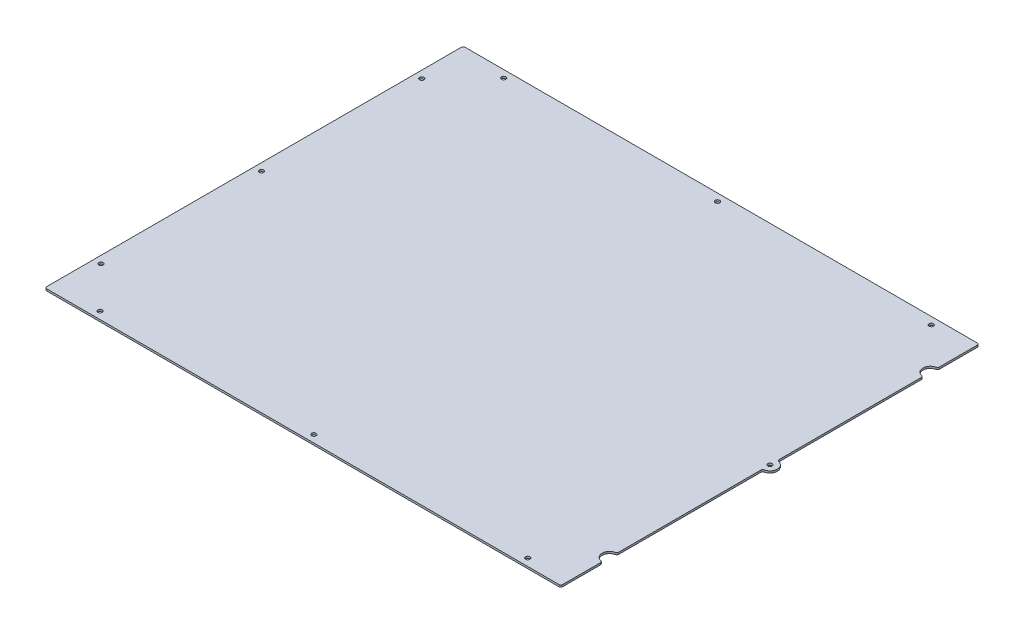
SolidWorks part; units mm, degrees
ref_plane "Front Plane" through (0, 0, 0) normal (0, 0, 1) x (1, 0, 0)
ref_plane "Top Plane" through (0, 0, 0) normal (0, 1, 0) x (1, 0, 0)
ref_plane "Right Plane" through (0, 0, 0) normal (1, 0, 0) x (0, 0, -1)
sketch "Sketch1" plane through (0, 0, 0) normal (0, 1, 0) x (1, 0, 0)
  line L0 (332.232, 273.304) -> (332.232, 219.202) construction
  line L1 (-341.884, -273.304) -> (332.232, -273.304)
  line L2 (-341.884, -273.304) -> (-341.884, 273.304)
  line L3 (-341.884, 273.304) -> (332.232, 273.304)
  line L4 (332.232, -219.202) -> (332.232, -273.304) construction
  line L5 (-341.884, -273.304) -> (341.884, 273.304) construction
  line L6 (-341.884, 273.304) -> (341.884, -273.304) construction
  line L7 (332.232, 273.304) -> (332.232, 219.202)
  line L8 (332.232, 199.898) -> (332.232, 9.652) construction
  line L9 (332.232, 199.898) -> (332.232, 9.652)
  line L10 (332.232, -9.652) -> (332.232, -199.898) construction
  line L11 (332.232, -9.652) -> (332.232, -199.898)
  line L12 (332.232, -219.202) -> (332.232, -273.304)
  arc A0 (332.232, -199.898) -> (332.232, -219.202) centre (332.232, -209.55) ccw
  arc A1 (332.232, -9.652) -> (332.232, 9.652) centre (332.232, 0) ccw
  arc A2 (332.232, 219.202) -> (332.232, 199.898) centre (332.232, 209.55) ccw
  point P0 (0, 0)
  dimension "D4" = 273.304
  dimension "D6" = 19.304
  dimension "D7" = 63.754
  dimension "D3" = 63.754
  dimension "D1" = 674.116
  dimension "D2" = 546.608
extrude "Boss-Extrude1" add sketch "Sketch1" along normal blind 2.54
hole_wizard "#1 (0.228) Diameter Hole2" positions "Sketch4" profile "Sketch5" hole size "#1" standard "ANSI Inch" end condition through all
sketch "Sketch4" plane through (0, 2.54, 0) normal (0, 1, 0) x (1, 0, 0)
  point P0 (332.232, 0)
sketch "Sketch5" plane through (332.232, 2.54, 0) normal (1, 0, 0) x (0, 0, 1)
  line L0 (0, 0) -> (0, 2.54)
  line L1 (0, 2.54) -> (2.8956, 2.54)
  line L2 (2.8956, 2.54) -> (2.8956, 0)
  line L5 (2.8956, 0) -> (0, 0)
  line L11 (0, -6.35) -> (0, 107.95) construction
  dimension "Thru Hole Dia." = 5.7912
  dimension "Thru Hole Depth" = 2.54
fillet "Fillet2" radius 2.54 10 edges at (-341.884, 1.27, -273.304) (-341.884, 1.27, 273.304) (332.232, 1.27, 273.304) (332.232, 1.27, 219.202) (332.232, 1.27, 199.898) (332.232, 1.27, 9.652) (332.232, 1.27, -9.652) (332.232, 1.27, -199.898) (332.232, 1.27, -219.202) (332.232, 1.27, -273.304)
hole_wizard "#1 (0.228) Diameter Hole3" positions "Sketch6" profile "Sketch7" hole size "#1" standard "ANSI Inch" end condition through all
sketch "Sketch6" plane through (0, 2.54, 0) normal (0, 1, 0) x (1, 0, 0)
  point P0 (-279.4, 263.652)
  point P3 (-332.232, 209.55)
  point P6 (0, 263.652)
  point P9 (279.4, 263.652)
  point P12 (279.4, -263.652)
  point P15 (0, -263.652)
  point P18 (-279.4, -263.652)
  point P21 (-332.232, -209.55)
  point P24 (-332.232, 0)
sketch "Sketch7" plane through (-279.4, 2.54, -263.652) normal (1, 0, 0) x (0, 0, 1)
  line L0 (0, 0) -> (0, 2.54)
  line L1 (0, 2.54) -> (2.8956, 2.54)
  line L2 (2.8956, 2.54) -> (2.8956, 0)
  line L5 (2.8956, 0) -> (0, 0)
  line L11 (0, -6.35) -> (0, 107.95) construction
  dimension "Thru Hole Dia." = 5.7912
  dimension "Thru Hole Depth" = 2.54
sketch "Sketch8" plane through (0, 2.54, 0) normal (0, 1, 0) x (1, 0, 0)
  line L1 (-322.58, 254) -> (322.58, 254) construction
  line L2 (-322.58, 254) -> (-322.58, -254) construction
  line L3 (-322.58, -254) -> (322.58, -254) construction
  line L4 (322.58, 254) -> (322.58, -254) construction
  line L6 (-341.884, 270.764) -> (-341.884, -270.764) construction
  line L7 (329.692, 273.304) -> (-339.344, 273.304) construction
  line L9 (-282.2575, 254) -> (-282.2575, -254) construction
  line L10 (-255.3758, 254) -> (-255.3758, -254) construction
  line L11 (-228.4942, 254) -> (-228.4942, -254) construction
  line L12 (-201.6125, 254) -> (-201.6125, -254) construction
  line L13 (-174.7308, 254) -> (-174.7308, -254) construction
  line L14 (-147.8492, 254) -> (-147.8492, -254) construction
  line L15 (-120.9675, 254) -> (-120.9675, -254) construction
  line L16 (-94.0858, 254) -> (-94.0858, -254) construction
  line L17 (-67.2042, 254) -> (-67.2042, -254) construction
  line L18 (-40.3225, 254) -> (-40.3225, -254) construction
  line L19 (-13.4408, 254) -> (-13.4408, -254) construction
  line L20 (13.4408, 254) -> (13.4408, -254) construction
  line L21 (40.3225, 254) -> (40.3225, -254) construction
  line L22 (67.2042, 254) -> (67.2042, -254) construction
  line L23 (94.0858, 254) -> (94.0858, -254) construction
  line L24 (120.9675, 254) -> (120.9675, -254) construction
  line L25 (147.8492, 254) -> (147.8492, -254) construction
  line L26 (174.7308, 254) -> (174.7308, -254) construction
  line L27 (201.6125, 254) -> (201.6125, -254) construction
  line L28 (228.4942, 254) -> (228.4942, -254) construction
  line L29 (255.3758, 254) -> (255.3758, -254) construction
  line L30 (282.2575, 254) -> (282.2575, -254) construction
  line L31 (309.1392, 254) -> (309.1392, -254) construction
  line L32 (-322.58, 190.5) -> (322.58, 190.5) construction
  line L34 (-318.2832, 145.034) -> (-299.9952, 145.034)
  line L35 (-318.2832, 145.034) -> (-318.2832, 235.966)
  line L36 (-318.2832, 235.966) -> (-299.9952, 235.966)
  line L37 (-299.9952, 145.034) -> (-299.9952, 235.966)
  line L38 (-318.2832, 145.034) -> (-299.9952, 235.966) construction
  line L39 (-318.2832, 235.966) -> (-299.9952, 145.034) construction
  line L40 (-273.1135, 145.034) -> (-273.1135, 235.966)
  line L41 (-291.4015, 145.034) -> (-291.4015, 235.966)
  line L42 (-291.4015, 145.034) -> (-273.1135, 145.034)
  line L43 (-264.5198, 235.966) -> (-246.2318, 235.966)
  line L44 (-246.2318, 145.034) -> (-246.2318, 235.966)
  line L45 (-264.5198, 145.034) -> (-264.5198, 235.966)
  line L46 (-264.5198, 145.034) -> (-246.2318, 145.034)
  line L51 (-210.7565, 235.966) -> (-192.4685, 235.966)
  line L52 (-192.4685, 145.034) -> (-192.4685, 235.966)
  line L53 (-210.7565, 145.034) -> (-210.7565, 235.966)
  line L54 (-210.7565, 145.034) -> (-192.4685, 145.034)
  line L55 (-183.8748, 235.966) -> (-165.5868, 235.966)
  line L56 (-165.5868, 145.034) -> (-165.5868, 235.966)
  line L57 (-183.8748, 145.034) -> (-183.8748, 235.966)
  line L58 (-183.8748, 145.034) -> (-165.5868, 145.034)
  line L59 (-156.9932, 235.966) -> (-138.7052, 235.966)
  line L60 (-138.7052, 145.034) -> (-138.7052, 235.966)
  line L61 (-156.9932, 145.034) -> (-156.9932, 235.966)
  line L62 (-156.9932, 145.034) -> (-138.7052, 145.034)
  line L63 (-130.1115, 235.966) -> (-111.8235, 235.966)
  line L64 (-111.8235, 145.034) -> (-111.8235, 235.966)
  line L65 (-130.1115, 145.034) -> (-130.1115, 235.966)
  line L66 (-130.1115, 145.034) -> (-111.8235, 145.034)
  line L71 (-76.3482, 235.966) -> (-58.0602, 235.966)
  line L72 (-58.0602, 145.034) -> (-58.0602, 235.966)
  line L73 (-76.3482, 145.034) -> (-76.3482, 235.966)
  line L74 (-76.3482, 145.034) -> (-58.0602, 145.034)
  line L75 (-49.4665, 235.966) -> (-31.1785, 235.966)
  line L76 (-31.1785, 145.034) -> (-31.1785, 235.966)
  line L77 (-49.4665, 145.034) -> (-49.4665, 235.966)
  line L78 (-49.4665, 145.034) -> (-31.1785, 145.034)
  line L79 (-22.5848, 235.966) -> (-4.2968, 235.966)
  line L80 (-4.2968, 145.034) -> (-4.2968, 235.966)
  line L81 (-22.5848, 145.034) -> (-22.5848, 235.966)
  line L82 (-22.5848, 145.034) -> (-4.2968, 145.034)
  line L83 (4.2968, 235.966) -> (22.5848, 235.966)
  line L84 (22.5848, 145.034) -> (22.5848, 235.966)
  line L85 (4.2968, 145.034) -> (4.2968, 235.966)
  line L86 (4.2968, 145.034) -> (22.5848, 145.034)
  line L87 (31.1785, 235.966) -> (49.4665, 235.966)
  line L88 (49.4665, 145.034) -> (49.4665, 235.966)
  line L89 (31.1785, 145.034) -> (31.1785, 235.966)
  line L90 (31.1785, 145.034) -> (49.4665, 145.034)
  line L91 (58.0602, 235.966) -> (76.3482, 235.966)
  line L92 (76.3482, 145.034) -> (76.3482, 235.966)
  line L93 (58.0602, 145.034) -> (58.0602, 235.966)
  line L94 (58.0602, 145.034) -> (76.3482, 145.034)
  line L95 (87.286, 237.109) -> (100.8857, 237.109)
  line L96 (87.286, 143.891) -> (100.8857, 143.891)
  line L97 (221.6943, 143.891) -> (235.294, 143.891)
  line L98 (221.6943, 237.109) -> (235.294, 237.109)
  line L99 (111.8235, 235.966) -> (130.1115, 235.966)
  line L100 (130.1115, 145.034) -> (130.1115, 235.966)
  line L101 (111.8235, 145.034) -> (111.8235, 235.966)
  line L102 (111.8235, 145.034) -> (130.1115, 145.034)
  line L103 (138.7052, 235.966) -> (156.9932, 235.966)
  line L104 (156.9932, 145.034) -> (156.9932, 235.966)
  line L105 (138.7052, 145.034) -> (138.7052, 235.966)
  line L106 (138.7052, 145.034) -> (156.9932, 145.034)
  line L107 (165.5868, 235.966) -> (183.8748, 235.966)
  line L108 (183.8748, 145.034) -> (183.8748, 235.966)
  line L109 (165.5868, 145.034) -> (165.5868, 235.966)
  line L110 (165.5868, 145.034) -> (183.8748, 145.034)
  line L111 (192.4685, 235.966) -> (210.7565, 235.966)
  line L112 (210.7565, 145.034) -> (210.7565, 235.966)
  line L113 (192.4685, 145.034) -> (192.4685, 235.966)
  line L114 (192.4685, 145.034) -> (210.7565, 145.034)
  line L119 (246.2318, 235.966) -> (264.5198, 235.966)
  line L120 (264.5198, 145.034) -> (264.5198, 235.966)
  line L121 (246.2318, 145.034) -> (246.2318, 235.966)
  line L122 (246.2318, 145.034) -> (264.5198, 145.034)
  line L123 (273.1135, 235.966) -> (291.4015, 235.966)
  line L124 (291.4015, 145.034) -> (291.4015, 235.966)
  line L125 (273.1135, 145.034) -> (273.1135, 235.966)
  line L126 (273.1135, 145.034) -> (291.4015, 145.034)
  line L127 (299.9952, 235.966) -> (318.2832, 235.966)
  line L128 (318.2832, 145.034) -> (318.2832, 235.966)
  line L129 (299.9952, 145.034) -> (299.9952, 235.966)
  line L130 (299.9952, 145.034) -> (318.2832, 145.034)
  line L131 (-291.4015, 108.966) -> (-273.1135, 108.966)
  line L132 (-273.1135, 18.034) -> (-273.1135, 108.966)
  line L133 (-291.4015, 18.034) -> (-291.4015, 108.966)
  line L134 (-291.4015, 18.034) -> (-273.1135, 18.034)
  line L135 (-264.5198, 108.966) -> (-246.2318, 108.966)
  line L136 (-246.2318, 18.034) -> (-246.2318, 108.966)
  line L137 (-264.5198, 18.034) -> (-264.5198, 108.966)
  line L138 (-264.5198, 18.034) -> (-246.2318, 18.034)
  line L139 (-100.8857, 237.109) -> (-87.286, 237.109)
  line L140 (-100.8857, 143.891) -> (-87.286, 143.891)
  line L143 (-210.7565, 108.966) -> (-192.4685, 108.966)
  line L144 (-192.4685, 18.034) -> (-192.4685, 108.966)
  line L145 (-210.7565, 18.034) -> (-210.7565, 108.966)
  line L146 (-210.7565, 18.034) -> (-192.4685, 18.034)
  line L147 (-183.8748, 108.966) -> (-165.5868, 108.966)
  line L148 (-165.5868, 18.034) -> (-165.5868, 108.966)
  line L149 (-183.8748, 18.034) -> (-183.8748, 108.966)
  line L150 (-183.8748, 18.034) -> (-165.5868, 18.034)
  line L151 (-156.9932, 108.966) -> (-138.7052, 108.966)
  line L152 (-138.7052, 18.034) -> (-138.7052, 108.966)
  line L153 (-156.9932, 18.034) -> (-156.9932, 108.966)
  line L154 (-156.9932, 18.034) -> (-138.7052, 18.034)
  line L155 (-130.1115, 108.966) -> (-111.8235, 108.966)
  line L156 (-111.8235, 18.034) -> (-111.8235, 108.966)
  line L157 (-130.1115, 18.034) -> (-130.1115, 108.966)
  line L158 (-130.1115, 18.034) -> (-111.8235, 18.034)
  line L163 (-76.3482, 108.966) -> (-58.0602, 108.966)
  line L164 (-58.0602, 18.034) -> (-58.0602, 108.966)
  line L165 (-76.3482, 18.034) -> (-76.3482, 108.966)
  line L166 (-76.3482, 18.034) -> (-58.0602, 18.034)
  line L167 (-49.4665, 108.966) -> (-31.1785, 108.966)
  line L168 (-31.1785, 18.034) -> (-31.1785, 108.966)
  line L169 (-49.4665, 18.034) -> (-49.4665, 108.966)
  line L170 (-49.4665, 18.034) -> (-31.1785, 18.034)
  line L171 (-22.5848, 108.966) -> (-4.2968, 108.966)
  line L172 (-4.2968, 18.034) -> (-4.2968, 108.966)
  line L173 (-22.5848, 18.034) -> (-22.5848, 108.966)
  line L174 (-22.5848, 18.034) -> (-4.2968, 18.034)
  line L175 (4.2968, 108.966) -> (22.5848, 108.966)
  line L176 (22.5848, 18.034) -> (22.5848, 108.966)
  line L177 (4.2968, 18.034) -> (4.2968, 108.966)
  line L178 (4.2968, 18.034) -> (22.5848, 18.034)
  line L179 (31.1785, 108.966) -> (49.4665, 108.966)
  line L180 (49.4665, 18.034) -> (49.4665, 108.966)
  line L181 (31.1785, 18.034) -> (31.1785, 108.966)
  line L182 (31.1785, 18.034) -> (49.4665, 18.034)
  line L183 (58.0602, 108.966) -> (76.3482, 108.966)
  line L184 (76.3482, 18.034) -> (76.3482, 108.966)
  line L185 (58.0602, 18.034) -> (58.0602, 108.966)
  line L186 (58.0602, 18.034) -> (76.3482, 18.034)
  line L191 (111.8235, 108.966) -> (130.1115, 108.966)
  line L192 (130.1115, 18.034) -> (130.1115, 108.966)
  line L193 (111.8235, 18.034) -> (111.8235, 108.966)
  line L194 (111.8235, 18.034) -> (130.1115, 18.034)
  line L195 (138.7052, 108.966) -> (156.9932, 108.966)
  line L196 (156.9932, 18.034) -> (156.9932, 108.966)
  line L197 (138.7052, 18.034) -> (138.7052, 108.966)
  line L198 (138.7052, 18.034) -> (156.9932, 18.034)
  line L199 (165.5868, 108.966) -> (183.8748, 108.966)
  line L200 (183.8748, 18.034) -> (183.8748, 108.966)
  line L201 (165.5868, 18.034) -> (165.5868, 108.966)
  line L202 (165.5868, 18.034) -> (183.8748, 18.034)
  line L203 (192.4685, 108.966) -> (210.7565, 108.966)
  line L204 (210.7565, 18.034) -> (210.7565, 108.966)
  line L205 (192.4685, 18.034) -> (192.4685, 108.966)
  line L206 (192.4685, 18.034) -> (210.7565, 18.034)
  line L211 (246.2318, 108.966) -> (264.5198, 108.966)
  line L212 (264.5198, 18.034) -> (264.5198, 108.966)
  line L213 (246.2318, 18.034) -> (246.2318, 108.966)
  line L214 (246.2318, 18.034) -> (264.5198, 18.034)
  line L215 (273.1135, 108.966) -> (291.4015, 108.966)
  line L216 (291.4015, 18.034) -> (291.4015, 108.966)
  line L217 (273.1135, 18.034) -> (273.1135, 108.966)
  line L218 (273.1135, 18.034) -> (291.4015, 18.034)
  line L219 (299.9952, 108.966) -> (318.2832, 108.966)
  line L220 (318.2832, 18.034) -> (318.2832, 108.966)
  line L221 (299.9952, 18.034) -> (299.9952, 108.966)
  line L222 (299.9952, 18.034) -> (318.2832, 18.034)
  line L223 (-291.4015, -18.034) -> (-273.1135, -18.034)
  line L224 (-273.1135, -108.966) -> (-273.1135, -18.034)
  line L225 (-291.4015, -108.966) -> (-291.4015, -18.034)
  line L226 (-291.4015, -108.966) -> (-273.1135, -108.966)
  line L227 (-264.5198, -18.034) -> (-246.2318, -18.034)
  line L228 (-246.2318, -108.966) -> (-246.2318, -18.034)
  line L229 (-264.5198, -108.966) -> (-264.5198, -18.034)
  line L230 (-264.5198, -108.966) -> (-246.2318, -108.966)
  line L235 (-210.7565, -18.034) -> (-192.4685, -18.034)
  line L236 (-192.4685, -108.966) -> (-192.4685, -18.034)
  line L237 (-210.7565, -108.966) -> (-210.7565, -18.034)
  line L238 (-210.7565, -108.966) -> (-192.4685, -108.966)
  line L239 (-183.8748, -18.034) -> (-165.5868, -18.034)
  line L240 (-165.5868, -108.966) -> (-165.5868, -18.034)
  line L241 (-183.8748, -108.966) -> (-183.8748, -18.034)
  line L242 (-183.8748, -108.966) -> (-165.5868, -108.966)
  line L243 (-156.9932, -18.034) -> (-138.7052, -18.034)
  line L244 (-138.7052, -108.966) -> (-138.7052, -18.034)
  line L245 (-156.9932, -108.966) -> (-156.9932, -18.034)
  line L246 (-156.9932, -108.966) -> (-138.7052, -108.966)
  line L247 (-130.1115, -18.034) -> (-111.8235, -18.034)
  line L248 (-111.8235, -108.966) -> (-111.8235, -18.034)
  line L249 (-130.1115, -108.966) -> (-130.1115, -18.034)
  line L250 (-130.1115, -108.966) -> (-111.8235, -108.966)
  line L255 (-76.3482, -18.034) -> (-58.0602, -18.034)
  line L256 (-58.0602, -108.966) -> (-58.0602, -18.034)
  line L257 (-76.3482, -108.966) -> (-76.3482, -18.034)
  line L258 (-76.3482, -108.966) -> (-58.0602, -108.966)
  line L259 (-49.4665, -18.034) -> (-31.1785, -18.034)
  line L260 (-31.1785, -108.966) -> (-31.1785, -18.034)
  line L261 (-49.4665, -108.966) -> (-49.4665, -18.034)
  line L262 (-49.4665, -108.966) -> (-31.1785, -108.966)
  line L263 (-22.5848, -18.034) -> (-4.2968, -18.034)
  line L264 (-4.2968, -108.966) -> (-4.2968, -18.034)
  line L265 (-22.5848, -108.966) -> (-22.5848, -18.034)
  line L266 (-22.5848, -108.966) -> (-4.2968, -108.966)
  line L267 (4.2968, -18.034) -> (22.5848, -18.034)
  line L268 (22.5848, -108.966) -> (22.5848, -18.034)
  line L269 (4.2968, -108.966) -> (4.2968, -18.034)
  line L270 (4.2968, -108.966) -> (22.5848, -108.966)
  line L271 (31.1785, -18.034) -> (49.4665, -18.034)
  line L272 (49.4665, -108.966) -> (49.4665, -18.034)
  line L273 (31.1785, -108.966) -> (31.1785, -18.034)
  line L274 (31.1785, -108.966) -> (49.4665, -108.966)
  line L275 (58.0602, -18.034) -> (76.3482, -18.034)
  line L276 (76.3482, -108.966) -> (76.3482, -18.034)
  line L277 (58.0602, -108.966) -> (58.0602, -18.034)
  line L278 (58.0602, -108.966) -> (76.3482, -108.966)
  line L283 (111.8235, -18.034) -> (130.1115, -18.034)
  line L284 (130.1115, -108.966) -> (130.1115, -18.034)
  line L285 (111.8235, -108.966) -> (111.8235, -18.034)
  line L286 (111.8235, -108.966) -> (130.1115, -108.966)
  line L287 (138.7052, -18.034) -> (156.9932, -18.034)
  line L288 (156.9932, -108.966) -> (156.9932, -18.034)
  line L289 (138.7052, -108.966) -> (138.7052, -18.034)
  line L290 (138.7052, -108.966) -> (156.9932, -108.966)
  line L291 (165.5868, -18.034) -> (183.8748, -18.034)
  line L292 (183.8748, -108.966) -> (183.8748, -18.034)
  line L293 (165.5868, -108.966) -> (165.5868, -18.034)
  line L294 (165.5868, -108.966) -> (183.8748, -108.966)
  line L295 (192.4685, -18.034) -> (210.7565, -18.034)
  line L296 (210.7565, -108.966) -> (210.7565, -18.034)
  line L297 (192.4685, -108.966) -> (192.4685, -18.034)
  line L298 (192.4685, -108.966) -> (210.7565, -108.966)
  line L303 (246.2318, -18.034) -> (264.5198, -18.034)
  line L304 (264.5198, -108.966) -> (264.5198, -18.034)
  line L305 (246.2318, -108.966) -> (246.2318, -18.034)
  line L306 (246.2318, -108.966) -> (264.5198, -108.966)
  line L307 (273.1135, -18.034) -> (291.4015, -18.034)
  line L308 (291.4015, -108.966) -> (291.4015, -18.034)
  line L309 (273.1135, -108.966) -> (273.1135, -18.034)
  line L310 (273.1135, -108.966) -> (291.4015, -108.966)
  line L311 (299.9952, -18.034) -> (318.2832, -18.034)
  line L312 (318.2832, -108.966) -> (318.2832, -18.034)
  line L313 (299.9952, -108.966) -> (299.9952, -18.034)
  line L314 (299.9952, -108.966) -> (318.2832, -108.966)
  line L315 (-291.4015, -145.034) -> (-273.1135, -145.034)
  line L316 (-273.1135, -235.966) -> (-273.1135, -145.034)
  line L317 (-291.4015, -235.966) -> (-291.4015, -145.034)
  line L318 (-291.4015, -235.966) -> (-273.1135, -235.966)
  line L319 (-264.5198, -145.034) -> (-246.2318, -145.034)
  line L320 (-246.2318, -235.966) -> (-246.2318, -145.034)
  line L321 (-264.5198, -235.966) -> (-264.5198, -145.034)
  line L322 (-264.5198, -235.966) -> (-246.2318, -235.966)
  line L327 (-210.7565, -145.034) -> (-192.4685, -145.034)
  line L328 (-192.4685, -235.966) -> (-192.4685, -145.034)
  line L329 (-210.7565, -235.966) -> (-210.7565, -145.034)
  line L330 (-210.7565, -235.966) -> (-192.4685, -235.966)
  line L331 (-183.8748, -145.034) -> (-165.5868, -145.034)
  line L332 (-165.5868, -235.966) -> (-165.5868, -145.034)
  line L333 (-183.8748, -235.966) -> (-183.8748, -145.034)
  line L334 (-183.8748, -235.966) -> (-165.5868, -235.966)
  line L335 (-156.9932, -145.034) -> (-138.7052, -145.034)
  line L336 (-138.7052, -235.966) -> (-138.7052, -145.034)
  line L337 (-156.9932, -235.966) -> (-156.9932, -145.034)
  line L338 (-156.9932, -235.966) -> (-138.7052, -235.966)
  line L339 (-130.1115, -145.034) -> (-111.8235, -145.034)
  line L340 (-111.8235, -235.966) -> (-111.8235, -145.034)
  line L341 (-130.1115, -235.966) -> (-130.1115, -145.034)
  line L342 (-130.1115, -235.966) -> (-111.8235, -235.966)
  line L347 (-76.3482, -145.034) -> (-58.0602, -145.034)
  line L348 (-58.0602, -235.966) -> (-58.0602, -145.034)
  line L349 (-76.3482, -235.966) -> (-76.3482, -145.034)
  line L350 (-76.3482, -235.966) -> (-58.0602, -235.966)
  line L351 (-49.4665, -145.034) -> (-31.1785, -145.034)
  line L352 (-31.1785, -235.966) -> (-31.1785, -145.034)
  line L353 (-49.4665, -235.966) -> (-49.4665, -145.034)
  line L354 (-49.4665, -235.966) -> (-31.1785, -235.966)
  line L355 (-22.5848, -145.034) -> (-4.2968, -145.034)
  line L356 (-4.2968, -235.966) -> (-4.2968, -145.034)
  line L357 (-22.5848, -235.966) -> (-22.5848, -145.034)
  line L358 (-22.5848, -235.966) -> (-4.2968, -235.966)
  line L359 (4.2968, -145.034) -> (22.5848, -145.034)
  line L360 (22.5848, -235.966) -> (22.5848, -145.034)
  line L361 (4.2968, -235.966) -> (4.2968, -145.034)
  line L362 (4.2968, -235.966) -> (22.5848, -235.966)
  line L363 (31.1785, -145.034) -> (49.4665, -145.034)
  line L364 (49.4665, -235.966) -> (49.4665, -145.034)
  line L365 (31.1785, -235.966) -> (31.1785, -145.034)
  line L366 (31.1785, -235.966) -> (49.4665, -235.966)
  line L367 (58.0602, -145.034) -> (76.3482, -145.034)
  line L368 (76.3482, -235.966) -> (76.3482, -145.034)
  line L369 (58.0602, -235.966) -> (58.0602, -145.034)
  line L370 (58.0602, -235.966) -> (76.3482, -235.966)
  line L375 (111.8235, -145.034) -> (130.1115, -145.034)
  line L376 (130.1115, -235.966) -> (130.1115, -145.034)
  line L377 (111.8235, -235.966) -> (111.8235, -145.034)
  line L378 (111.8235, -235.966) -> (130.1115, -235.966)
  line L379 (138.7052, -145.034) -> (156.9932, -145.034)
  line L380 (156.9932, -235.966) -> (156.9932, -145.034)
  line L381 (138.7052, -235.966) -> (138.7052, -145.034)
  line L382 (138.7052, -235.966) -> (156.9932, -235.966)
  line L383 (165.5868, -145.034) -> (183.8748, -145.034)
  line L384 (183.8748, -235.966) -> (183.8748, -145.034)
  line L385 (165.5868, -235.966) -> (165.5868, -145.034)
  line L386 (165.5868, -235.966) -> (183.8748, -235.966)
  line L387 (192.4685, -145.034) -> (210.7565, -145.034)
  line L388 (210.7565, -235.966) -> (210.7565, -145.034)
  line L389 (192.4685, -235.966) -> (192.4685, -145.034)
  line L390 (192.4685, -235.966) -> (210.7565, -235.966)
  line L395 (246.2318, -145.034) -> (264.5198, -145.034)
  line L396 (264.5198, -235.966) -> (264.5198, -145.034)
  line L397 (246.2318, -235.966) -> (246.2318, -145.034)
  line L398 (246.2318, -235.966) -> (264.5198, -235.966)
  line L399 (273.1135, -145.034) -> (291.4015, -145.034)
  line L400 (291.4015, -235.966) -> (291.4015, -145.034)
  line L401 (273.1135, -235.966) -> (273.1135, -145.034)
  line L402 (273.1135, -235.966) -> (291.4015, -235.966)
  line L403 (299.9952, -145.034) -> (318.2832, -145.034)
  line L404 (318.2832, -235.966) -> (318.2832, -145.034)
  line L405 (299.9952, -235.966) -> (299.9952, -145.034)
  line L406 (299.9952, -235.966) -> (318.2832, -235.966)
  line L407 (-318.2832, 108.966) -> (-299.9952, 108.966)
  line L408 (-299.9952, 18.034) -> (-299.9952, 108.966)
  line L409 (-318.2832, 18.034) -> (-318.2832, 108.966)
  line L410 (-318.2832, 18.034) -> (-299.9952, 18.034)
  line L411 (-318.2832, -18.034) -> (-299.9952, -18.034)
  line L412 (-299.9952, -108.966) -> (-299.9952, -18.034)
  line L413 (-318.2832, -108.966) -> (-318.2832, -18.034)
  line L414 (-318.2832, -108.966) -> (-299.9952, -108.966)
  line L415 (-318.2832, -145.034) -> (-299.9952, -145.034)
  line L416 (-299.9952, -235.966) -> (-299.9952, -145.034)
  line L417 (-318.2832, -235.966) -> (-318.2832, -145.034)
  line L418 (-318.2832, -235.966) -> (-299.9952, -235.966)
  line L419 (-237.6382, 235.966) -> (-219.3502, 235.966) [skipped]
  line L420 (-219.3502, 145.034) -> (-219.3502, 235.966) [skipped]
  line L421 (-237.6382, 145.034) -> (-237.6382, 235.966) [skipped]
  line L422 (-237.6382, 145.034) -> (-219.3502, 145.034) [skipped]
  line L423 (-237.6382, 108.966) -> (-219.3502, 108.966) [skipped]
  line L424 (-219.3502, 18.034) -> (-219.3502, 108.966) [skipped]
  line L425 (-237.6382, 18.034) -> (-237.6382, 108.966) [skipped]
  line L426 (-237.6382, 18.034) -> (-219.3502, 18.034) [skipped]
  line L427 (-237.6382, -18.034) -> (-219.3502, -18.034) [skipped]
  line L428 (-219.3502, -108.966) -> (-219.3502, -18.034) [skipped]
  line L429 (-237.6382, -108.966) -> (-237.6382, -18.034) [skipped]
  line L430 (-237.6382, -108.966) -> (-219.3502, -108.966) [skipped]
  line L431 (-237.6382, -145.034) -> (-219.3502, -145.034) [skipped]
  line L432 (-219.3502, -235.966) -> (-219.3502, -145.034) [skipped]
  line L433 (-237.6382, -235.966) -> (-237.6382, -145.034) [skipped]
  line L434 (-237.6382, -235.966) -> (-219.3502, -235.966) [skipped]
  line L435 (-103.2298, 235.966) -> (-84.9418, 235.966) [skipped]
  line L436 (-84.9418, 145.034) -> (-84.9418, 235.966) [skipped]
  line L437 (-103.2298, 145.034) -> (-103.2298, 235.966) [skipped]
  line L438 (-103.2298, 145.034) -> (-84.9418, 145.034) [skipped]
  line L439 (-103.2298, 108.966) -> (-84.9418, 108.966) [skipped]
  line L440 (-84.9418, 18.034) -> (-84.9418, 108.966) [skipped]
  line L441 (-103.2298, 18.034) -> (-103.2298, 108.966) [skipped]
  line L442 (-103.2298, 18.034) -> (-84.9418, 18.034) [skipped]
  line L443 (-103.2298, -18.034) -> (-84.9418, -18.034) [skipped]
  line L444 (-84.9418, -108.966) -> (-84.9418, -18.034) [skipped]
  line L445 (-103.2298, -108.966) -> (-103.2298, -18.034) [skipped]
  line L446 (-103.2298, -108.966) -> (-84.9418, -108.966) [skipped]
  line L447 (-103.2298, -145.034) -> (-84.9418, -145.034) [skipped]
  line L448 (-84.9418, -235.966) -> (-84.9418, -145.034) [skipped]
  line L449 (-103.2298, -235.966) -> (-103.2298, -145.034) [skipped]
  line L450 (-103.2298, -235.966) -> (-84.9418, -235.966) [skipped]
  line L451 (219.3502, 235.966) -> (237.6382, 235.966) [skipped]
  line L452 (237.6382, 145.034) -> (237.6382, 235.966) [skipped]
  line L453 (219.3502, 145.034) -> (219.3502, 235.966) [skipped]
  line L454 (219.3502, 145.034) -> (237.6382, 145.034) [skipped]
  line L455 (219.3502, 108.966) -> (237.6382, 108.966) [skipped]
  line L456 (237.6382, 18.034) -> (237.6382, 108.966) [skipped]
  line L457 (219.3502, 18.034) -> (219.3502, 108.966) [skipped]
  line L458 (219.3502, 18.034) -> (237.6382, 18.034) [skipped]
  line L459 (219.3502, -18.034) -> (237.6382, -18.034) [skipped]
  line L460 (237.6382, -108.966) -> (237.6382, -18.034) [skipped]
  line L461 (219.3502, -108.966) -> (219.3502, -18.034) [skipped]
  line L462 (219.3502, -108.966) -> (237.6382, -108.966) [skipped]
  line L463 (219.3502, -145.034) -> (237.6382, -145.034) [skipped]
  line L464 (237.6382, -235.966) -> (237.6382, -145.034) [skipped]
  line L465 (219.3502, -235.966) -> (219.3502, -145.034) [skipped]
  line L466 (219.3502, -235.966) -> (237.6382, -235.966) [skipped]
  line L467 (84.9418, 235.966) -> (103.2298, 235.966) [skipped]
  line L468 (103.2298, 145.034) -> (103.2298, 235.966) [skipped]
  line L469 (84.9418, 145.034) -> (84.9418, 235.966) [skipped]
  line L470 (84.9418, 145.034) -> (103.2298, 145.034) [skipped]
  line L471 (84.9418, 108.966) -> (103.2298, 108.966) [skipped]
  line L472 (103.2298, 18.034) -> (103.2298, 108.966) [skipped]
  line L473 (84.9418, 18.034) -> (84.9418, 108.966) [skipped]
  line L474 (84.9418, 18.034) -> (103.2298, 18.034) [skipped]
  line L475 (84.9418, -18.034) -> (103.2298, -18.034) [skipped]
  line L476 (103.2298, -108.966) -> (103.2298, -18.034) [skipped]
  line L477 (84.9418, -108.966) -> (84.9418, -18.034) [skipped]
  line L478 (84.9418, -108.966) -> (103.2298, -108.966) [skipped]
  line L479 (84.9418, -145.034) -> (103.2298, -145.034) [skipped]
  line L480 (103.2298, -235.966) -> (103.2298, -145.034) [skipped]
  line L481 (84.9418, -235.966) -> (84.9418, -145.034) [skipped]
  line L482 (84.9418, -235.966) -> (103.2298, -235.966) [skipped]
  line L483 (-291.4015, 235.966) -> (-273.1135, 235.966) [skipped]
  circle A0 centre (-309.1392, 241.808) radius 1.905
  circle A1 centre (-282.2575, 241.808) radius 1.905
  circle A2 centre (-255.3758, 241.808) radius 1.905
  circle A4 centre (-201.6125, 241.808) radius 1.905
  circle A5 centre (-174.7308, 241.808) radius 1.905
  circle A6 centre (-147.8492, 241.808) radius 1.905
  circle A7 centre (-120.9675, 241.808) radius 1.905
  circle A8 centre (-94.0858, 242.189) radius 1.905
  circle A9 centre (-67.2042, 241.808) radius 1.905
  circle A10 centre (-40.3225, 241.808) radius 1.905
  circle A11 centre (-13.4408, 241.808) radius 1.905
  circle A12 centre (13.4408, 241.808) radius 1.905
  circle A13 centre (40.3225, 241.808) radius 1.905
  circle A14 centre (67.2042, 241.808) radius 1.905
  circle A15 centre (94.0858, 242.189) radius 1.905
  circle A16 centre (120.9675, 241.808) radius 1.905
  circle A17 centre (147.8492, 241.808) radius 1.905
  circle A18 centre (174.7308, 241.808) radius 1.905
  circle A19 centre (201.6125, 241.808) radius 1.905
  circle A20 centre (228.4942, 242.189) radius 1.905
  circle A21 centre (255.3758, 241.808) radius 1.905
  circle A22 centre (282.2575, 241.808) radius 1.905
  circle A23 centre (309.1392, 241.808) radius 1.905
  circle A24 centre (-282.2575, 114.808) radius 1.905
  circle A25 centre (-255.3758, 114.808) radius 1.905
  circle A27 centre (-201.6125, 114.808) radius 1.905
  circle A28 centre (-174.7308, 114.808) radius 1.905
  circle A29 centre (-147.8492, 114.808) radius 1.905
  circle A30 centre (-120.9675, 114.808) radius 1.905
  circle A32 centre (-67.2042, 114.808) radius 1.905
  circle A33 centre (-40.3225, 114.808) radius 1.905
  circle A34 centre (-13.4408, 114.808) radius 1.905
  circle A35 centre (13.4408, 114.808) radius 1.905
  circle A36 centre (40.3225, 114.808) radius 1.905
  circle A37 centre (67.2042, 114.808) radius 1.905
  circle A39 centre (120.9675, 114.808) radius 1.905
  circle A40 centre (147.8492, 114.808) radius 1.905
  circle A41 centre (174.7308, 114.808) radius 1.905
  circle A42 centre (201.6125, 114.808) radius 1.905
  circle A44 centre (255.3758, 114.808) radius 1.905
  circle A45 centre (282.2575, 114.808) radius 1.905
  circle A46 centre (309.1392, 114.808) radius 1.905
  circle A47 centre (-282.2575, -12.192) radius 1.905
  circle A48 centre (-255.3758, -12.192) radius 1.905
  circle A50 centre (-201.6125, -12.192) radius 1.905
  circle A51 centre (-174.7308, -12.192) radius 1.905
  circle A52 centre (-147.8492, -12.192) radius 1.905
  circle A53 centre (-120.9675, -12.192) radius 1.905
  circle A55 centre (-67.2042, -12.192) radius 1.905
  circle A56 centre (-40.3225, -12.192) radius 1.905
  circle A57 centre (-13.4408, -12.192) radius 1.905
  circle A58 centre (13.4408, -12.192) radius 1.905
  circle A59 centre (40.3225, -12.192) radius 1.905
  circle A60 centre (67.2042, -12.192) radius 1.905
  circle A62 centre (120.9675, -12.192) radius 1.905
  circle A63 centre (147.8492, -12.192) radius 1.905
  circle A64 centre (174.7308, -12.192) radius 1.905
  circle A65 centre (201.6125, -12.192) radius 1.905
  circle A67 centre (255.3758, -12.192) radius 1.905
  circle A68 centre (282.2575, -12.192) radius 1.905
  circle A69 centre (309.1392, -12.192) radius 1.905
  circle A70 centre (-282.2575, -139.192) radius 1.905
  circle A71 centre (-255.3758, -139.192) radius 1.905
  circle A73 centre (-201.6125, -139.192) radius 1.905
  circle A74 centre (-174.7308, -139.192) radius 1.905
  circle A75 centre (-147.8492, -139.192) radius 1.905
  circle A76 centre (-120.9675, -139.192) radius 1.905
  circle A78 centre (-67.2042, -139.192) radius 1.905
  circle A79 centre (-40.3225, -139.192) radius 1.905
  circle A80 centre (-13.4408, -139.192) radius 1.905
  circle A81 centre (13.4408, -139.192) radius 1.905
  circle A82 centre (40.3225, -139.192) radius 1.905
  circle A83 centre (67.2042, -139.192) radius 1.905
  circle A85 centre (120.9675, -139.192) radius 1.905
  circle A86 centre (147.8492, -139.192) radius 1.905
  circle A87 centre (174.7308, -139.192) radius 1.905
  circle A88 centre (201.6125, -139.192) radius 1.905
  circle A90 centre (255.3758, -139.192) radius 1.905
  circle A91 centre (282.2575, -139.192) radius 1.905
  circle A92 centre (309.1392, -139.192) radius 1.905
  circle A93 centre (-309.1392, 114.808) radius 1.905
  circle A94 centre (-309.1392, -12.192) radius 1.905
  circle A95 centre (-309.1392, -139.192) radius 1.905
  circle A96 centre (-228.4942, 241.808) radius 1.905 [skipped]
  circle A97 centre (-228.4942, 114.808) radius 1.905 [skipped]
  circle A98 centre (-228.4942, -12.192) radius 1.905 [skipped]
  circle A99 centre (-228.4942, -139.192) radius 1.905 [skipped]
  circle A100 centre (-94.0858, 241.808) radius 1.905 [skipped]
  circle A101 centre (-94.0858, 114.808) radius 1.905 [skipped]
  circle A102 centre (-94.0858, -12.192) radius 1.905 [skipped]
  circle A103 centre (-94.0858, -139.192) radius 1.905 [skipped]
  circle A104 centre (228.4942, 241.808) radius 1.905 [skipped]
  circle A105 centre (228.4942, 114.808) radius 1.905 [skipped]
  circle A106 centre (228.4942, -12.192) radius 1.905 [skipped]
  circle A107 centre (228.4942, -139.192) radius 1.905 [skipped]
  circle A108 centre (94.0858, 241.808) radius 1.905 [skipped]
  circle A109 centre (94.0858, 114.808) radius 1.905 [skipped]
  circle A110 centre (94.0858, -12.192) radius 1.905 [skipped]
  circle A111 centre (94.0858, -139.192) radius 1.905 [skipped]
  spline S6 degree 3 poles (-87.286, 237.109) (-86.7772, 235.1744) (-85.81, 231.2804) (-84.146, 223.5175) (-82.5419, 213.8049) (-81.3884, 202.153) (-81.0036, 190.5) (-81.3884, 178.847) (-82.5419, 167.1951) (-84.146, 157.4825) (-85.81, 149.7196) (-86.7772, 145.8256) (-87.286, 143.891) knots -0.002043 -0.002043 -0.002043 -0.002043 0.060713 0.123468 0.248979 0.374489 0.5 0.625511 0.751021 0.876532 0.939287 1.002043 1.002043 1.002043 1.002043
  spline S7 degree 3 poles (-100.8857, 143.891) (-101.3945, 145.8256) (-102.3616, 149.7196) (-104.0257, 157.4825) (-105.6297, 167.1951) (-106.7833, 178.847) (-107.1681, 190.5) (-106.7833, 202.153) (-105.6297, 213.8049) (-104.0257, 223.5175) (-102.3616, 231.2804) (-101.3945, 235.1744) (-100.8857, 237.109) knots -0.002043 -0.002043 -0.002043 -0.002043 0.060713 0.123468 0.248979 0.374489 0.5 0.625511 0.751021 0.876532 0.939287 1.002043 1.002043 1.002043 1.002043
  spline S8 degree 3 poles (87.286, 143.891) (86.7772, 145.8256) (85.81, 149.7196) (84.146, 157.4825) (82.5419, 167.1951) (81.3884, 178.847) (81.0036, 190.5) (81.3884, 202.153) (82.5419, 213.8049) (84.146, 223.5175) (85.81, 231.2804) (86.7772, 235.1744) (87.286, 237.109) knots -0.002043 -0.002043 -0.002043 -0.002043 0.060713 0.123468 0.248979 0.374489 0.5 0.625511 0.751021 0.876532 0.939287 1.002043 1.002043 1.002043 1.002043
  spline S9 degree 3 poles (100.8857, 237.109) (101.3945, 235.1744) (102.3616, 231.2804) (104.0257, 223.5175) (105.6297, 213.8049) (106.7833, 202.153) (107.1681, 190.5) (106.7833, 178.847) (105.6297, 167.1951) (104.0257, 157.4825) (102.3616, 149.7196) (101.3945, 145.8256) (100.8857, 143.891) knots -0.002043 -0.002043 -0.002043 -0.002043 0.060713 0.123468 0.248979 0.374489 0.5 0.625511 0.751021 0.876532 0.939287 1.002043 1.002043 1.002043 1.002043
  spline S10 degree 3 poles (235.294, 237.109) (235.8028, 235.1744) (236.77, 231.2804) (238.434, 223.5175) (240.0381, 213.8049) (241.1916, 202.153) (241.5764, 190.5) (241.1916, 178.847) (240.0381, 167.1951) (238.434, 157.4825) (236.77, 149.7196) (235.8028, 145.8256) (235.294, 143.891) knots -0.002043 -0.002043 -0.002043 -0.002043 0.060713 0.123468 0.248979 0.374489 0.5 0.625511 0.751021 0.876532 0.939287 1.002043 1.002043 1.002043 1.002043
  spline S11 degree 3 poles (221.6943, 143.891) (221.1855, 145.8256) (220.2184, 149.7196) (218.5543, 157.4825) (216.9503, 167.1951) (215.7967, 178.847) (215.4119, 190.5) (215.7967, 202.153) (216.9503, 213.8049) (218.5543, 223.5175) (220.2184, 231.2804) (221.1855, 235.1744) (221.6943, 237.109) knots -0.002043 -0.002043 -0.002043 -0.002043 0.060713 0.123468 0.248979 0.374489 0.5 0.625511 0.751021 0.876532 0.939287 1.002043 1.002043 1.002043 1.002043
  point P62 (-309.1392, 190.5)
  dimension "D12" = 24
  dimension "D13" = 4
  dimension "D20" = 2
  dimension "D21" = 2
extrude "Cut-Extrude1" cut sketch "Sketch8" against normal through all rebuild error yes
